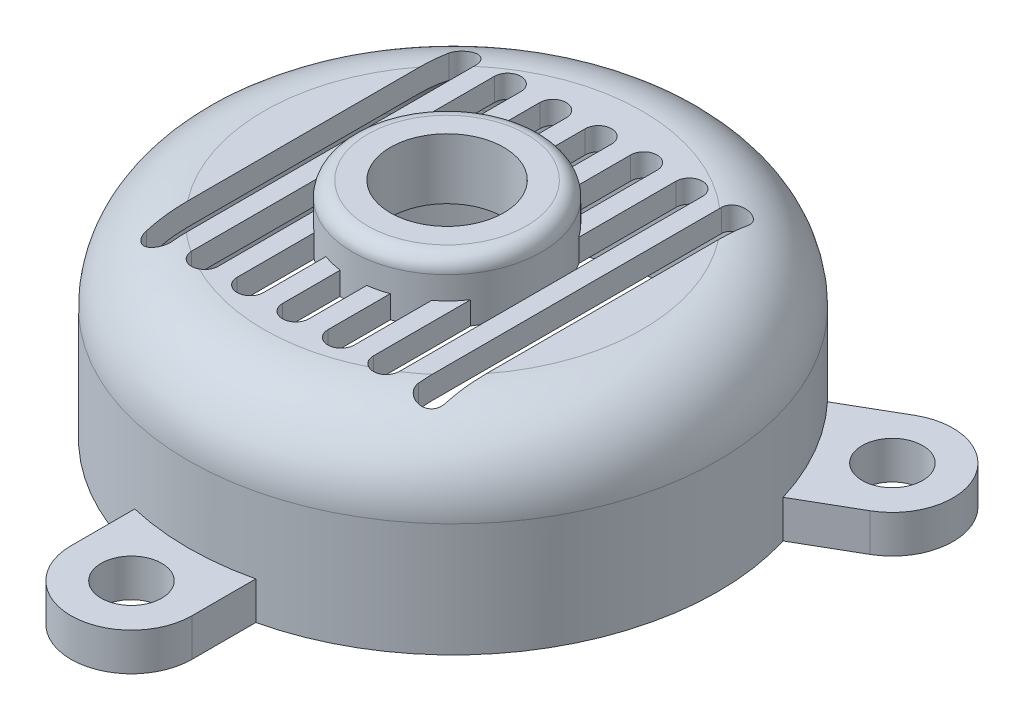
SolidWorks part; units mm, degrees
ref_plane "Front Plane" through (0, 0, 0) normal (0, 0, 1) x (1, 0, 0)
ref_plane "Top Plane" through (0, 0, 0) normal (0, 1, 0) x (1, 0, 0)
ref_plane "Right Plane" through (0, 0, 0) normal (1, 0, 0) x (0, 0, -1)
sketch "Sketch1" plane through (0, 0, 0) normal (0, 1, 0) x (1, 0, 0)
  circle A0 centre (0, 0.7922) radius 35
  dimension "D1" = 70
extrude "Boss-Extrude1" add sketch "Sketch1" along normal blind 25
fillet "Fillet1" radius 10 1 edges at (0, 25, 34.2078)
sketch "Sketch3" plane through (0, 0, 0) normal (0, -1, 0) x (1, 0, 0)
  line L0 (-8, 33.2813) -> (-8, 41.7078)
  line L1 (-8, 41.7078) -> (8, 41.7078) construction
  line L2 (8, 41.7078) -> (8, 33.2813)
  circle A0 centre (0, -0.7922) radius 35 construction
  circle A1 centre (0, -0.7922) radius 35
  arc A2 (8, 41.7078) -> (-8, 41.7078) centre (0, 41.7078) ccw
  circle A3 centre (0, 41.7078) radius 4
  circle M1 centre (0, -0.7922) radius 35
  dimension "D1" = 16
  dimension "D3" = 8
  dimension "D2" = 42.5
extrude "Boss-Extrude2" add sketch "Sketch3" against normal blind 5 contours L1 A2 | L2 L1 L0 M1 region at (-7.7707, 0, 37.4945)
pattern_circular "CirPattern1" count 3 over 360 about axis through (0, 25, -0.7922) along (0, -1, 0) of "Boss-Extrude2"
shell "Shell2" thickness 3 removed face at (0, 0, -0.7922)
sketch "Sketch6" plane through (0, 25, 0) normal (0, 1, 0) x (1, 0, 0)
  line L0 (0, 0) -> (0, 37.4148) construction
  line L1 (0, 37.4148) -> (0, -55.0857) construction
  line L2 (0, 0) -> (58.8999, 0) construction
  line L3 (58.8999, 0) -> (-70.3636, 0) construction
  line L4 (18, -20) -> (18, 20) construction
  line L5 (16.25, -20) -> (16.25, 20)
  line L6 (19.75, -20) -> (19.75, 20)
  arc A0 (16.25, -20) -> (19.75, -20) centre (18, -20) ccw
  arc A1 (19.75, 20) -> (16.25, 20) centre (18, 20) ccw
  point P8 (18, 0)
  point P13 (19.5674, -7.2543)
  point P14 (19.3698, 0)
  dimension "D1" = 3.5
  dimension "D2" = 40
  dimension "D3" = 18
extrude "Cut-Extrude1" cut sketch "Sketch6" against normal through all
sketch "Sketch7" plane through (0, 25, 0) normal (0, 1, 0) x (1, 0, 0)
  line L0 (0, 0) -> (54.9469, 0) construction
  line L1 (54.9469, 0) -> (-64.6318, 0) construction
pattern_linear "LPattern1" count 7 spacing 6 along (-1, 0, 0) of "Cut-Extrude1"
ref_plane "Plane1" through (0, 22, 0) normal (0, 1, 0) x (1, 0, 0)
sketch "Sketch8" plane through (0, 22, 0) normal (0, 1, 0) x (1, 0, 0)
  circle A0 centre (0, 0) radius 12.5
  dimension "D1" = 25
extrude "Boss-Extrude3" add sketch "Sketch8" along normal blind 8
sketch "Sketch9" plane through (0, 30, 0) normal (0, 1, 0) x (1, 0, 0)
  circle A0 centre (0, 0) radius 7.5
  dimension "D1" = 15
extrude "Cut-Extrude2" cut sketch "Sketch9" against normal through all
fillet "Fillet2" radius 2 1 edges at (0, 30, 12.5)
